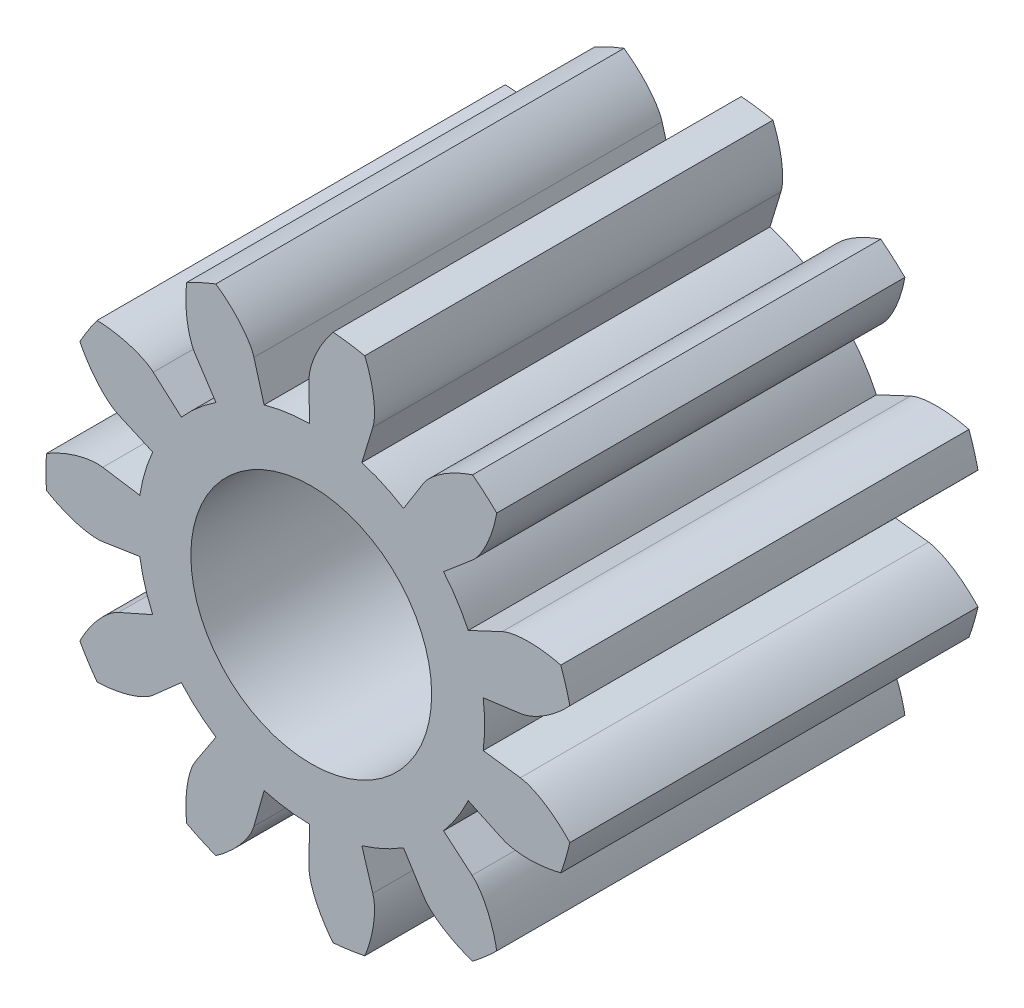
SolidWorks part; units mm, degrees
ref_plane "前视基准面" through (0, 0, 0) normal (0, 0, 1) x (1, 0, 0)
ref_plane "上视基准面" through (0, 0, 0) normal (0, 1, 0) x (1, 0, 0)
ref_plane "右视基准面" through (0, 0, 0) normal (1, 0, 0) x (0, 0, -1)
other "Configuration Table"
sketch "草图1" plane through (0, 0, 0) normal (0, 0, 1) x (1, 0, 0)
  line L0 (0, 0) -> (2.75, 0) construction
  line L1 (0, 0) -> (2.722, 0.3914) construction
  line L2 (0, 0) -> (2.5616, 0.3409)
  line L3 (2.722, 0.3914) -> (2.722, -0.3914) construction
  line L4 (0, 0) -> (2.5616, -0.3409)
  circle A0 centre (0, 0) radius 3.25
  circle A1 centre (0, 0) radius 2.75 construction
  circle A2 centre (0, 0) radius 2.125
  circle A3 centre (0, 0) radius 2.5842 construction
  circle A4 centre (0, 0) radius 1.475
  spline S0 degree 4 poles (2.5616, 0.3409) (2.5811, 0.3434) (2.6351, 0.3548) (2.7339, 0.3923) (2.8842, 0.4745) (3.0604, 0.6102) (3.2596, 0.8147) (3.4546, 1.0869) (3.6236, 1.4134) (3.7554, 1.787) (3.84, 2.1738) (3.8804, 2.5676) (3.8793, 2.9828) (3.8244, 3.4942) (3.6811, 4.0914) (3.4152, 4.754) (3.0092, 5.4353) (2.5105, 6.051) (1.9323, 6.5935) (1.2916, 7.0578) (0.5965, 7.4405) (-0.1332, 7.7406) (-0.9, 7.9569) (-1.5736, 8.0747) (-2.1793, 8.1235) (-2.6141, 8.1328) (-3.001, 8.1207) (-3.2567, 8.1034) (-3.6166, 8.0685) (-3.8867, 8.0264) (-4.1567, 7.9814) (-4.2916, 7.9504) (-4.3787, 7.9326) knots 0 0 0 0 0 0.005604 0.015718 0.02996 0.048734 0.068727 0.096889 0.125051 0.153212 0.181374 0.209535 0.237696 0.271429 0.327752 0.384075 0.440398 0.496721 0.553044 0.609367 0.66569 0.722013 0.778336 0.834659 0.86282 0.890982 0.909091 0.931818 0.954545 0.977273 1 1 1 1 1 construction
  spline S1 degree 4 poles (2.5616, 0.3409) (2.5811, 0.3434) (2.6351, 0.3548) (2.7339, 0.3923) (2.8842, 0.4745) (3.0604, 0.6102) (3.2596, 0.8147) (3.4546, 1.0869) (3.6236, 1.4134) (3.7554, 1.787) (3.84, 2.1738) (3.8804, 2.5676) (3.8793, 2.9828) (3.8244, 3.4942) (3.6811, 4.0914) (3.4152, 4.754) (3.0092, 5.4353) (2.5105, 6.051) (1.9323, 6.5935) (1.2916, 7.0578) (0.5965, 7.4405) (-0.1332, 7.7406) (-0.9, 7.9569) (-1.5736, 8.0747) (-2.1793, 8.1235) (-2.6141, 8.1328) (-2.9105, 8.1235) (-3.0577, 8.1158) (-3.1153, 8.1121) knots 0 0 0 0 0 0.005604 0.015718 0.02996 0.048734 0.068727 0.096889 0.125051 0.153212 0.181374 0.209535 0.237696 0.271429 0.327752 0.384075 0.440398 0.496721 0.553044 0.609367 0.66569 0.722013 0.778336 0.834659 0.86282 0.890982 0.909091 0.909091 0.909091 0.909091 0.909091
  spline S2 degree 4 poles (2.5616, -0.3409) (2.5811, -0.3434) (2.6351, -0.3548) (2.7339, -0.3923) (2.8842, -0.4745) (3.0604, -0.6102) (3.2596, -0.8147) (3.4546, -1.0869) (3.6236, -1.4134) (3.7554, -1.787) (3.84, -2.1738) (3.8804, -2.5676) (3.8793, -2.9828) (3.8244, -3.4942) (3.6811, -4.0914) (3.4152, -4.754) (3.0092, -5.4353) (2.5105, -6.051) (1.9323, -6.5935) (1.2916, -7.0578) (0.5965, -7.4405) (-0.1332, -7.7406) (-0.9, -7.9569) (-1.5736, -8.0747) (-2.1793, -8.1235) (-2.6141, -8.1328) (-3.001, -8.1207) (-3.2567, -8.1034) (-3.6166, -8.0685) (-3.8867, -8.0264) (-4.1567, -7.9814) (-4.2916, -7.9504) (-4.3787, -7.9326) knots 0 0 0 0 0 0.005604 0.015718 0.02996 0.048734 0.068727 0.096889 0.125051 0.153212 0.181374 0.209535 0.237696 0.271429 0.327752 0.384075 0.440398 0.496721 0.553044 0.609367 0.66569 0.722013 0.778336 0.834659 0.86282 0.890982 0.909091 0.931818 0.954545 0.977273 1 1 1 1 1 construction
  spline S3 degree 4 poles (2.5616, -0.3409) (2.5811, -0.3434) (2.6351, -0.3548) (2.7339, -0.3923) (2.8842, -0.4745) (3.0604, -0.6102) (3.2596, -0.8147) (3.4546, -1.0869) (3.6236, -1.4134) (3.7554, -1.787) (3.84, -2.1738) (3.8804, -2.5676) (3.8793, -2.9828) (3.8244, -3.4942) (3.6811, -4.0914) (3.4152, -4.754) (3.0092, -5.4353) (2.5105, -6.051) (1.9323, -6.5935) (1.2916, -7.0578) (0.5965, -7.4405) (-0.1332, -7.7406) (-0.9, -7.9569) (-1.5736, -8.0747) (-2.1793, -8.1235) (-2.6141, -8.1328) (-2.9105, -8.1235) (-3.0577, -8.1158) (-3.1153, -8.1121) knots 0 0 0 0 0 0.005604 0.015718 0.02996 0.048734 0.068727 0.096889 0.125051 0.153212 0.181374 0.209535 0.237696 0.271429 0.327752 0.384075 0.440398 0.496721 0.553044 0.609367 0.66569 0.722013 0.778336 0.834659 0.86282 0.890982 0.909091 0.909091 0.909091 0.909091 0.909091
  point P15 (2.722, 0)
  dimension "齿顶圆直径" = 6.5
  dimension "分度圆直径" = 5.5
  dimension "齿根圆直径" = 4.25
  dimension "基圆直径" = 5.1683
  dimension "内孔直径" = 2.95
  dimension "渐近线镜像线夹角" = 8.182
extrude "凸台-拉伸1" add sketch "草图1" along normal blind 5 contours A0 | A4
extrude "切除-拉伸1" cut sketch "草图1<3>" along normal through all contours A2 S3 A0 S1 region at (2.7676, 0, 0)
sketch "草图1<3>" plane through (0, 0, 0) normal (0, 0, 1) x (1, 0, 0) same geometry as "草图1"
pattern_circular "阵列(圆周)1" count 11 every 32.727 about axis through (0, 0, 5) along (0, 0, 1) of "切除-拉伸1"
equation "\"m\"= 0.5'模数"
equation "\"z\"= 11'齿数"
equation "\"a\"= 20度'压力角"
equation "\"d\"= \"m\" * \"z\"'分度圆直径"
equation "\"da\"= ( \"z\" + 2 ) * \"m\"'齿顶圆直径"
equation "\"df\"= ( \"z\" - 2.5 ) * \"m\"'齿根圆直径"
equation "\"s\"= 0.5 * PI * \"m\"'分度圆齿厚"
equation "\"r\"= 0.38 * \"m\"'齿根圆角"
equation "\"B\"= 0.3 * \"d\"'齿厚"
equation "\"db\"= \"m\" * \"z\" * cos ( \"a\" )'基圆直径"
equation "\"rb\"= \"db\" / 2'基圆半径"
equation "\"齿顶圆直径@草图1\"= \"da\""
equation "\"分度圆直径@草图1\"= \"d\""
equation "\"齿根圆直径@草图1\"= \"df\""
equation "\"基圆直径@草图1\"= \"db\""
equation "\"渐近线镜像线夹角@草图1\"= 360 / 4 / \"z\""
equation "\"h\"= 5'齿轮厚度"
equation "\"ir\"= 2.95'内孔直径"
equation "\"内孔直径@草图1\"= \"ir\""
equation "\"齿轮厚@凸台-拉伸1\"= \"h\""
equation "\"齿轮夹角@阵列(圆周)1\"= 360 / \"z\""
equation "\"齿数@阵列(圆周)1\"= \"z\""
